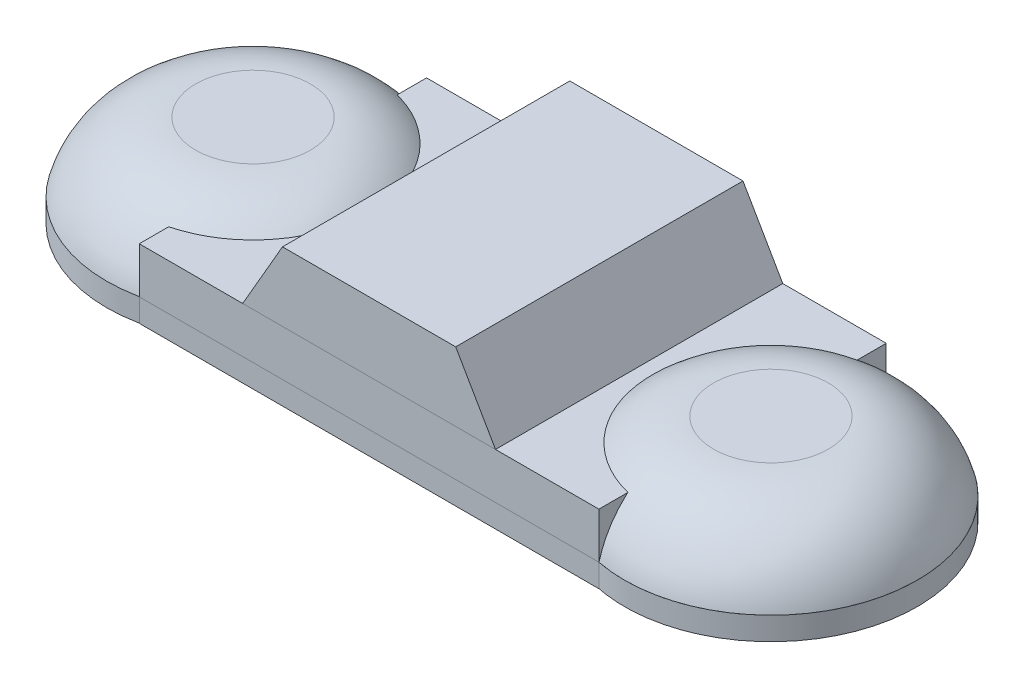
SolidWorks part; units mm, degrees
ref_plane "Front Plane" through (0, 0, 0) normal (0, 0, 1) x (1, 0, 0)
ref_plane "Top Plane" through (0, 0, 0) normal (0, 1, 0) x (1, 0, 0)
ref_plane "Right Plane" through (0, 0, 0) normal (1, 0, 0) x (0, 0, -1)
sketch "Sketch1" plane through (0, 0, 0) normal (0, 1, 0) x (1, 0, 0)
  line L0 (-0.9968, -0.6292) -> (1.0032, -0.6292)
  line L1 (1.0032, 0.3666) -> (1.0032, 0.6208)
  line L2 (1.0032, 0.6208) -> (-0.9968, 0.6208)
  line L3 (-0.9968, 0.6208) -> (-0.9968, 0.3656)
  line L4 (-0.9968, -0.6292) -> (-0.9968, -0.3741)
  line L5 (1.0032, -0.375) -> (1.0032, -0.6292)
  arc A0 (-0.9968, -0.3741) -> (-0.9968, 0.3656) centre (-1.1468, -0.0042) ccw
  arc A1 (1.0032, 0.3666) -> (1.0032, -0.375) centre (1.1532, -0.0042) ccw
  arc A2 (1.0032, 0.6208) -> (1.0032, -0.6292) centre (1.1532, -0.0042) cw
  arc A3 (-1.0032, 0.6208) -> (-1.0032, -0.6292) centre (-1.1532, -0.0042) ccw
extrude "Boss-Extrude1" add sketch "Sketch1" along normal blind 0.1 contours A1 L1 L2 L3 A0 L4 L0 L5 region at (0.0029, 0, 0.0042)
sketch "Sketch2" plane through (0, 0, 0) normal (0, -1, 0) x (1, 0, 0)
  line L0 (0, 0) -> (0, -0.8305) construction
  circle A1 centre (-1.1266, 0.0042) radius 0.6371
  circle A2 centre (1.1266, 0.0042) radius 0.6371
extrude "Boss-Extrude2" add sketch "Sketch2" against normal blind 0.1 separate body
sketch "Sketch4" plane through (0, 0.1, 0) normal (0, 1, 0) x (1, 0, 0)
  line L6 (1.0032, 0.3666) -> (1.0032, 0.6208)
  line L7 (1.0032, 0.6208) -> (-0.9968, 0.6208)
  line L8 (-0.9968, 0.6208) -> (-0.9968, 0.3656)
  line L9 (-0.9968, -0.3741) -> (-0.9968, -0.6292)
  line L10 (-0.9968, -0.6292) -> (1.0032, -0.6292)
  line L11 (1.0032, -0.6292) -> (1.0032, -0.375)
  line L12 (1.0032, 0.3666) -> (1.0032, 0.6208)
  line L13 (1.0032, 0.6208) -> (-0.9968, 0.6208)
  line L14 (-0.9968, 0.6208) -> (-0.9968, 0.3656)
  line L15 (-0.9968, -0.3741) -> (-0.9968, -0.6292)
  line L16 (-0.9968, -0.6292) -> (1.0032, -0.6292)
  line L17 (1.0032, -0.6292) -> (1.0032, -0.375)
  arc A2 (1.0032, 0.3666) -> (1.0032, -0.375) centre (1.1532, -0.0042) ccw
  arc A3 (-0.9968, -0.3741) -> (-0.9968, 0.3656) centre (-1.1468, -0.0042) ccw
  arc A4 (1.0032, 0.3666) -> (1.0032, -0.375) centre (1.1532, -0.0042) ccw
  arc A5 (-0.9968, -0.3741) -> (-0.9968, 0.3656) centre (-1.1468, -0.0042) ccw
  dimension "D1" = 0
extrude "Boss-Extrude3" add sketch "Sketch4" along normal blind 0.2 separate body
sketch "Sketch5" plane through (0, 0.1, 0) normal (0, 1, 0) x (1, 0, 0)
  circle A1 centre (1.1266, -0.0042) radius 0.6371
  circle A2 centre (1.1266, -0.0042) radius 0.6371
  dimension "D1" = 0
extrude "Boss-Extrude4" add sketch "Sketch5" along normal blind 0.3 separate body
sketch "Sketch6" plane through (0, 0.1, 0) normal (0, 1, 0) x (1, 0, 0)
  circle A1 centre (-1.1266, -0.0042) radius 0.6371
  circle A2 centre (-1.1266, -0.0042) radius 0.6371
  dimension "D1" = 0
extrude "Boss-Extrude5" add sketch "Sketch6" along normal blind 0.3 separate body
fillet "Fillet1" radius 0.4 1 edges at (1.1266, 0.4, 0.6413)
fillet "Fillet2" radius 0.4 1 edges at (-1.1266, 0.4, 0.6413)
sketch "Sketch10" plane through (0, 0.3, 0) normal (0, 1, 0) x (1, 0, 0)
  line L0 (0.5532, -0.6292) -> (0.5532, 0.6208)
  line L1 (-0.9968, -0.6292) -> (1.0032, -0.6292) construction
  line L2 (0.5532, -0.6292) -> (-0.5468, -0.6292)
  line L3 (1.0032, 0.6208) -> (-0.9968, 0.6208) construction
  line L4 (0.5532, 0.6208) -> (-0.5468, 0.6208)
  line L5 (-0.5468, 0.6208) -> (-0.5468, -0.6292)
extrude "Boss-Extrude6" add sketch "Sketch10" along normal blind 0.3
chamfer "Chamfer1" distance 0.3 angle 30 2 edges at (-0.5468, 0.6, 0.0042) (0.5532, 0.6, 0.0042) first distance on face at (-0.5468, 0.45, 0.0042) first distance on face at (0.5532, 0.45, 0.0042)
